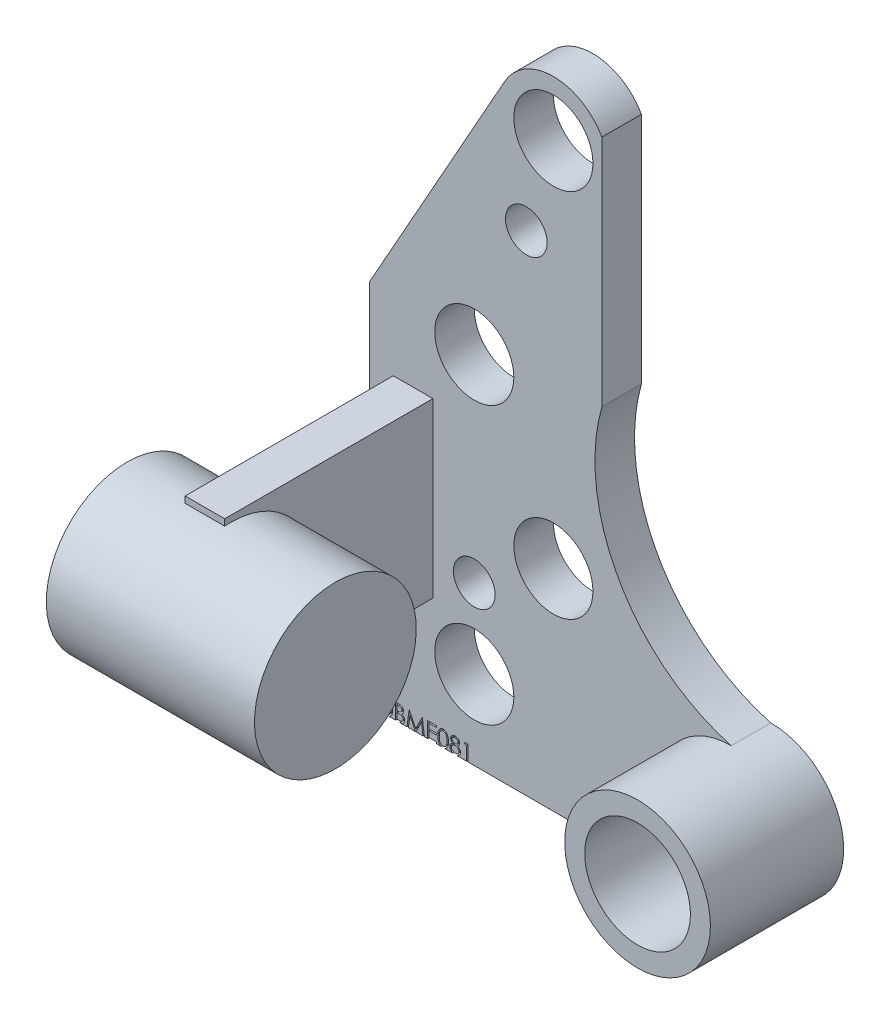
SolidWorks part; units mm, degrees
ref_plane "Front Plane" through (0, 0, 0) normal (0, 0, 1) x (1, 0, 0)
ref_plane "Top Plane" through (0, 0, 0) normal (0, 1, 0) x (1, 0, 0)
ref_plane "Right Plane" through (0, 0, 0) normal (1, 0, 0) x (0, 0, -1)
sketch "Sketch1" plane through (0, 0, 0) normal (0, 0, 1) x (1, 0, 0)
  line L0 (-50.3794, -38.0098) -> (-50.3794, 137.9902)
  line L1 (-50.3794, 137.9902) -> (14.712, 254.0598)
  line L2 (61.288, 254.0598) -> (61.288, 141.8915)
  line L3 (-50.3794, -38.0098) -> (123.4359, -38.0098)
  circle A0 centre (0, 0) radius 19
  circle A1 centre (0, 38) radius 10
  circle A2 centre (38, 63) radius 19
  circle A3 centre (0, 133) radius 19
  circle A4 centre (38, 241) radius 19
  circle A5 centre (25, 197) radius 10
  arc A6 (61.288, 254.0598) -> (14.712, 254.0598) centre (38, 241) ccw
  circle A7 centre (123.4359, -3.0098) radius 35
  circle A8 centre (123.4359, -3.0098) radius 25.4
  arc A9 (61.288, 141.8915) -> (123.4359, 31.9902) centre (146.9715, 117.8219) ccw
  dimension "D1" = 38
  dimension "D2" = 38
  dimension "D3" = 20
  dimension "D4" = 38
  dimension "D5" = 38
  dimension "D6" = 20
  dimension "D8" = 89
  dimension "D17" = 50.8
  dimension "D18" = 70
  dimension "D19" = 26.7
  dimension "D7" = 176
  dimension "D10" = 241
  dimension "D11" = 25
  dimension "D12" = 70
  dimension "D13" = 38
  dimension "D14" = 38
  dimension "D15" = 108
  dimension "D16" = 13
extrude "Boss-Extrude1" add sketch "Sketch1" along normal blind 19 contours A9 L2 A6 L1 L0 L3 A7 A5 A4 A3 A2 A1 A0 | A8 | A7 region at (17.7883, 83.0117, 0)
extrude "Boss-Extrude2" add sketch "Sketch1<6>" along normal blind 64 contours A7 A8 region at (89.4258, -3.0098, 0)
sketch "Sketch1<6>" plane through (0, 0, 0) normal (0, 0, 1) x (1, 0, 0) same geometry as "Sketch1"
sketch "Sketch2" plane through (0, 0, 19) normal (0, 0, 1) x (1, 0, 0)
  line L1 (-38.879, 104.7277) -> (-19.879, 104.7277)
  line L2 (-38.879, 104.7277) -> (-38.879, 21.7277)
  line L3 (-38.879, 21.7277) -> (-19.879, 21.7277)
  line L4 (-19.879, 104.7277) -> (-19.879, 21.7277)
  dimension "D1" = 83
  dimension "D2" = 19
sketch "Sketch5" plane through (0, 0, 19) normal (0, 0, 1) x (1, 0, 0)
  text T0 "20BME081" font "Century Gothic" height 7.5
extrude "Cut-Extrude1" cut sketch "Sketch5" against normal blind 5
extrude "Boss-Extrude5" add sketch "Sketch2" along normal blind 100
sketch "Sketch6" plane through (-19.879, 0, 0) normal (1, 0, 0) x (0, 0, -1)
  circle A1 centre (-115.8329, 62.9264) radius 38.8586
  point P2 (-96.4947, 64.6079)
  point P3 (-115.8329, 62.9264)
extrude "Boss-Extrude6" add sketch "Sketch6" against normal mid plane 100
